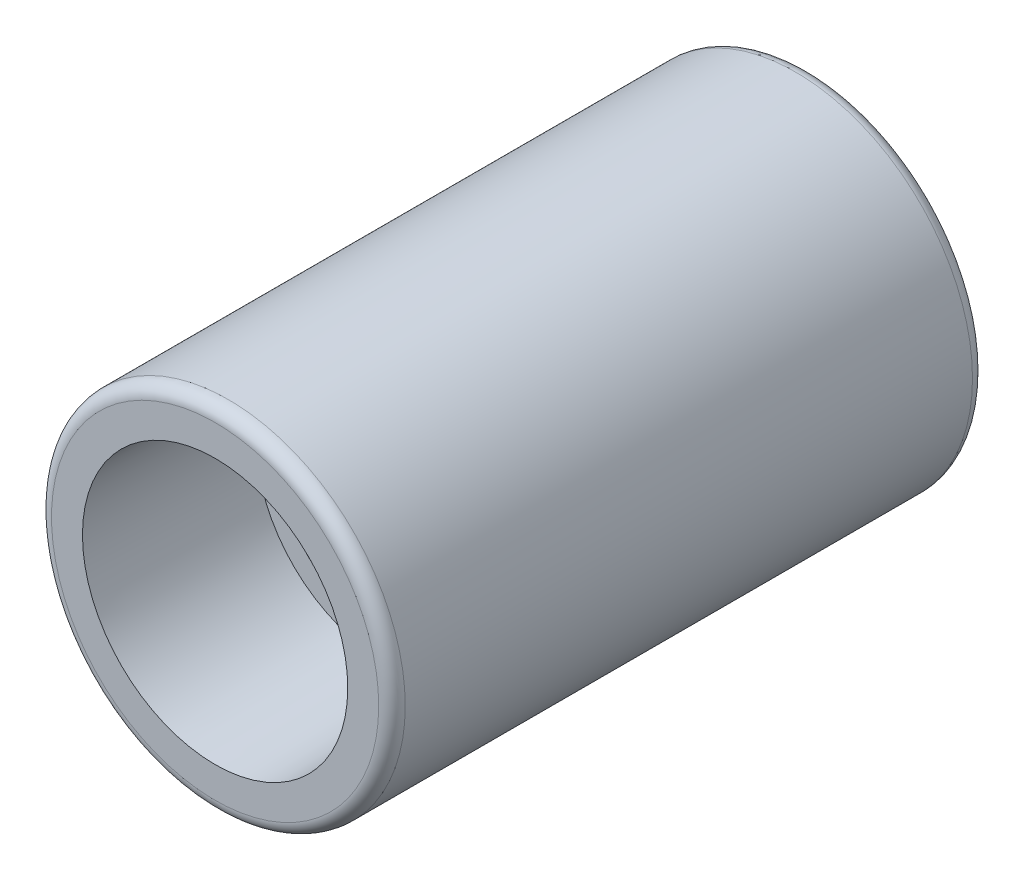
SolidWorks part; units mm, degrees
extrude "Body" add sketch "BodySch" along normal mid plane 47.752
sketch "BodySch" plane through (0, 0, 0) normal (0, 0, 1) x (1, 0, 0)
  circle A0 centre (0, 0) radius 14.224
  dimension "Dia" = 28.448
material "AISI 316  (SS)"
ref_plane "Front" through (0, 0, 0) normal (0, 0, 1) x (1, 0, 0)
ref_plane "Top" through (0, 0, 0) normal (0, 1, 0) x (1, 0, 0)
ref_plane "Right" through (0, 0, 0) normal (1, 0, 0) x (0, 0, -1)
sketch "FlowSch" plane through (0, 0, -23.876) normal (0, 0, 1) x (1, 0, 0)
  circle A0 centre (0, 0) radius 8.5344
  dimension "Dia" = 17.0688
extrude "Flow" cut sketch "FlowSch" along normal up to surface (47.752 mm away) up to face at (14.224, 0, 23.876)
sketch "ThreadSch" plane through (0, 0, 0) normal (1, 0, 0) x (0, 0, -1)
  line L0 (0, 0) -> (-23.876, 0) construction
  line L1 (-23.876, 0) -> (23.876, 0) construction
  line L2 (-10.32, 0) -> (-10.32, 10.2459)
  line L3 (-10.32, 10.2459) -> (-23.876, 10.668)
  line L4 (-23.876, 10.668) -> (-23.876, 0)
  line L5 (-23.876, 0) -> (-10.32, 0)
  line L6 (-23.876, 14.224) -> (-23.876, -14.224) construction
  dimension "D1" = 1.783
revolve "Thread" cut sketch "ThreadSch" angle 360 about L0
fillet "Fillet1" radius 1.0668 2 edges at (14.224, 0, 23.876) (14.224, 0, -23.876)
mirror "Mirror1" about plane through (0, 0, 0) normal (0, 0, 1) of "Thread"
sketch "Sketch1" plane through (0, 0, 0) normal (1, 0, 0) x (0, 0, -1)
  line L0 (-22.8092, 0) -> (22.8092, 0) construction
  line L1 (10.32, -10.2459) -> (10.32, 10.2459) construction
  line L2 (-10.32, 10.2459) -> (-10.32, -10.2459) construction
  point P0 (0, 0)
  point P1 (-10.32, 0)
  point P3 (10.32, 0)
other "CPoint1" parameters "Diameter"=12.7, "StubLength"=0
ref_axis "Axis1" through (0, 0, -20.32) along (0, 0, 1)
other "CPoint2" parameters "Diameter"=12.7, "StubLength"=0
ref_axis "Axis2" through (0, 0, 20.32) along (0, 0, -1)
other "RPoint1"
equation "\"EdgeRadius@Fillet1\" =  ( \"Dia@ThreadSch\" - \"Dia@FlowSch\" )  / 4"
